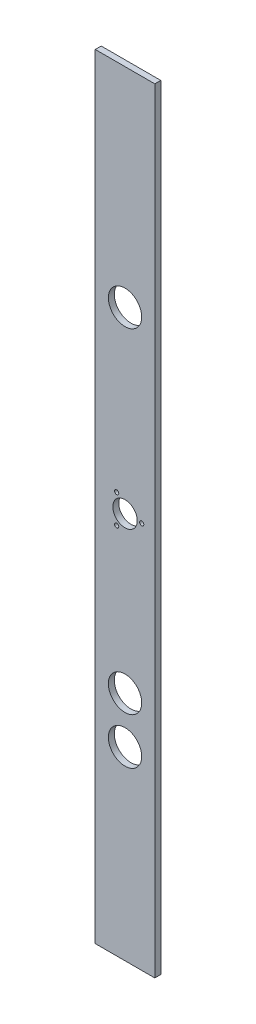
SolidWorks part; units mm, degrees
ref_plane "Plan de face" through (0, 0, 0) normal (0, 0, 1) x (1, 0, 0)
ref_plane "Plan de dessus" through (0, 0, 0) normal (0, 1, 0) x (1, 0, 0)
ref_plane "Plan de droite" through (0, 0, 0) normal (1, 0, 0) x (0, 0, -1)
sketch "Esquisse1" plane through (0, 0, 0) normal (0, 0, 1) x (1, 0, 0)
  line L0 (18, -312.8756) -> (25, -325)
  line L1 (0, 0) -> (50, 0)
  line L2 (0, 0) -> (0, -650)
  line L3 (0, -650) -> (50, -650)
  line L4 (50, 0) -> (50, -650)
  line L5 (25, -325) -> (39, -325)
  line L6 (25, -325) -> (18, -337.1244)
  circle A0 centre (25, -325) radius 10.25
  circle A1 centre (25, -325) radius 14
  circle A2 centre (25, -494.5) radius 14
  circle A3 centre (18, -312.8756) radius 1.75
  circle A4 centre (18, -337.1244) radius 1.75
  circle A5 centre (39, -325) radius 1.75
  circle A6 centre (25, -455.5) radius 14
  circle A7 centre (25, -175) radius 14
  dimension "D5" = 20.5
  dimension "D6" = 120
  dimension "D7" = 28
  dimension "D8" = 3.5
  dimension "D9" = 3.5
  dimension "D10" = 3.5
  dimension "D13" = 28
  dimension "D14" = 28
  dimension "D15" = 28
  dimension "D1" = 50
  dimension "D2" = 650
  dimension "D3" = 25
  dimension "D4" = 325
  dimension "D11" = 120
  dimension "D12" = 90
  dimension "D16" = 25
  dimension "D17" = 25
  dimension "D18" = 130.5
  dimension "D19" = 39
  dimension "D20" = 150
  dimension "D21" = 25
extrude "Boss.-Extru.1" add sketch "Esquisse1" along normal blind 5 contours L4 L1 L2 L3 A5 A1 A4 A3 | A5 A1 A3 L0 A0 L5 | A4 L6 A0 L0 A3 A1 | A5 L5 A0 L6 A4 A1 region at (30.1275, -316.1189, 0) region at (14.7449, -325, 0) region at (30.1275, -333.8811, 0) region at (25, -6.5192, 0)
chamfer "Chanfrein1" distance 1 angle 45 3 edges at (19.75, -337.1244, 0) (19.75, -312.8756, 0) (40.75, -325, 0)
